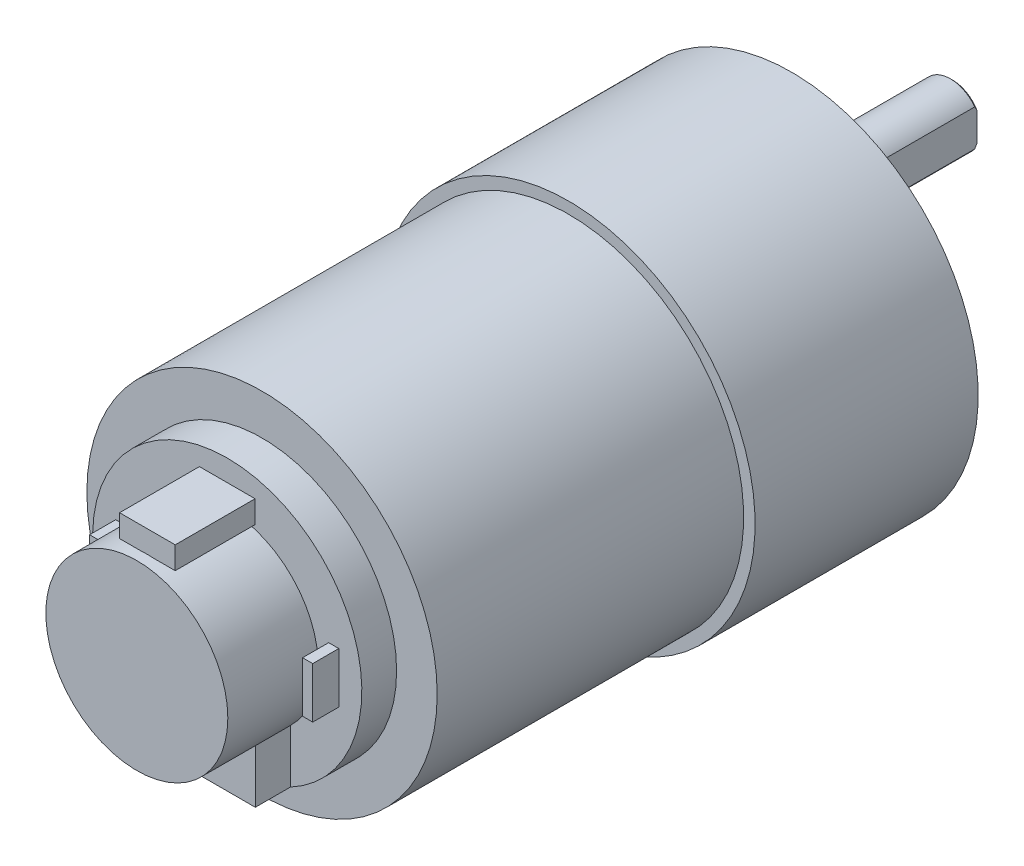
SolidWorks part; units mm, degrees
material "Plain Carbon Steel"
ref_plane "Front Plane" through (0, 0, 0) normal (0, 0, 1) x (1, 0, 0)
ref_plane "Top Plane" through (0, 0, 0) normal (0, 1, 0) x (1, 0, 0)
ref_plane "Right Plane" through (0, 0, 0) normal (1, 0, 0) x (0, 0, -1)
sketch "Sketch1" plane through (0, 0, 0) normal (0, 0, 1) x (1, 0, 0)
  line L0 (0, 0) -> (-7, 0)
  line L1 (0, 0) -> (-17.272, 0)
  line L2 (0, 0) -> (0, 17.272)
  line L3 (0, 0) -> (0, -15.5)
  line L4 (-4.6, 1.8) -> (-4.6, -1.8)
  line L5 (0, 0) -> (0, -15.5) construction
  circle A0 centre (0, 0) radius 17.272
  circle A1 centre (-7, 0) radius 3
  circle A2 centre (-7, 0) radius 6
  circle A3 centre (0, -15.5) radius 1.5
  circle A4 centre (-13.4234, -7.75) radius 1.5
  circle A5 centre (-13.4234, 7.75) radius 1.5
  circle A6 centre (0, 15.5) radius 1.5
  circle A7 centre (13.4234, 7.75) radius 1.5
  circle A8 centre (13.4234, -7.75) radius 1.5
  point P28 (0, -0.9391)
  point P31 (0, 0)
  point P35 (0, 0)
  dimension "D1" = 34.544
  dimension "D2" = 7
  dimension "D4" = 6
  dimension "D3" = 12
  dimension "D8" = 6
  dimension "D6" = 15.5
  dimension "D7" = 3
  dimension "D5" = 2.4
  dimension "D9" = 15.5
extrude "Boss-Extrude1" add sketch "Sketch1" along normal blind 52.22 contours A0
extrude "Boss-Extrude2" add sketch "Sketch1<3>" against normal blind 6.5 contours A2 A1 | L4 A1 L1 | L1 A1 L4 | L1 A2 A1 | L1 A1 L4 | L4 A1 L1 region at (-7, -5.8658, 0) region at (-2.5, 0.1342, 0) region at (-4.3578, -0.685, 0) region at (-4.3578, 0.685, 0) region at (-7.1451, -1.3055, 0) region at (-7.1451, 1.3055, 0)
sketch "Sketch1<3>" plane through (0, 0, 0) normal (0, 0, 1) x (1, 0, 0) same geometry as "Sketch1"
extrude "Boss-Extrude3" add sketch "Sketch1<4>" against normal blind 22.86 contours L4 A1 L1 | L1 A1 L4 region at (-7.1451, -1.3055, 0) region at (-7.1451, 1.3055, 0)
sketch "Sketch1<4>" plane through (0, 0, 0) normal (0, 0, 1) x (1, 0, 0) same geometry as "Sketch1"
extrude "Boss-Extrude4" add sketch "Sketch1<5>" against normal blind 10.668 contours L4 A1 | L4 A1 L1 region at (-4.3578, -0.685, 0) region at (-4.3578, 0.685, 0)
sketch "Sketch1<5>" plane through (0, 0, 0) normal (0, 0, 1) x (1, 0, 0) same geometry as "Sketch1"
sketch "Sketch2" plane through (0, 0, 52.22) normal (0, 0, 1) x (1, 0, 0)
  line L0 (0, 17.272) -> (0, -17.272) construction
  line L1 (17.272, 0) -> (-17.272, 0) construction
  line L2 (-11, 2.5) -> (-10, 2.5)
  line L3 (-11, 2.5) -> (-11, -2.5)
  line L4 (-11, -2.5) -> (-10, -2.5)
  line L5 (-10, 2.5) -> (-10, -2.5)
  line L6 (10, 2.5) -> (10, -2.5)
  line L7 (11, -2.5) -> (10, -2.5)
  line L8 (11, 2.5) -> (11, -2.5)
  line L9 (11, 2.5) -> (10, 2.5)
  circle A0 centre (0, 0) radius 17.272 construction
  dimension "D1" = 5
  dimension "D2" = 1
  dimension "D3" = 2.5
  dimension "D4" = 10
extrude "Boss-Extrude5" add sketch "Sketch2" along normal blind 6
sketch "Sketch4" plane through (0, 0, 0) normal (0, 0, -1) x (-1, 0, 0)
  circle A0 centre (0, 0) radius 18.4
  dimension "D1" = 36.8
extrude "Boss-Extrude6" add sketch "Sketch4" against normal blind 22
hole_wizard "Tap Drill for M3 Tap1" positions "Sketch8" profile "Sketch7" hole size "M3" standard "ISO"
sketch "Sketch8" plane through (0, 0, 0) normal (0, 0, -1) x (-1, 0, 0)
  point P0 (-13.4234, -7.75)
  point P3 (0, -15.5)
  point P6 (0, 15.5)
  point P9 (13.4234, 7.75)
  point P12 (13.4234, -7.75)
  point P15 (-13.4234, 7.75)
sketch "Sketch7" plane through (13.4234, -7.75, 0) normal (1, 0, 0) x (0, 1, 0)
  line L0 (0, 0) -> (0, 3.7511)
  line L1 (0, 3.7511) -> (1.25, 3)
  line L2 (1.25, 3) -> (1.25, 0)
  line L5 (1.25, 0) -> (0, 0)
  line L10 (0, 3.7511) -> (-1.25, 3) construction
  line L11 (0, -6.35) -> (0, 107.95) construction
  dimension "Hole Dia." = 2.5
  dimension "Hole Depth" = 3
  dimension "Drill Angle" = 118
sketch "Sketch9" plane through (0, 0, 52.22) normal (0, 0, 1) x (1, 0, 0)
  circle A0 centre (0, 0) radius 13.2715
  dimension "D1" = 26.543
extrude "Boss-Extrude7" add sketch "Sketch9" along normal blind 3.429
sketch "Sketch10" plane through (0, 0, 55.649) normal (0, 0, 1) x (1, 0, 0)
  circle A0 centre (0, 0) radius 8.9726
  dimension "D1" = 17.9451
extrude "Boss-Extrude8" add sketch "Sketch10" along normal blind 8.9154
sketch "Sketch11" plane through (0, 0, 55.649) normal (0, 0, 1) x (1, 0, 0)
  line L1 (6.223, -11.7221) -> (-6.223, -11.7221)
  line L2 (6.223, -11.7221) -> (6.223, -5.6769)
  line L3 (6.223, -5.6769) -> (-6.223, -5.6769)
  line L4 (-6.223, -11.7221) -> (-6.223, -5.6769)
  circle A0 centre (0, 0) radius 13.2715 construction
  circle A1 centre (0, 0) radius 13.2715 construction
  dimension "D1" = 6.0452
  dimension "D2" = 12.446
extrude "Boss-Extrude9" add sketch "Sketch11" along normal blind 3.4544
sketch "Sketch12" plane through (0, 0, 55.649) normal (0, 0, 1) x (1, 0, 0)
  line L1 (2.7432, 8.9535) -> (-2.7432, 8.9535)
  line L2 (2.7432, 8.9535) -> (2.7432, 11.1633)
  line L3 (2.7432, 11.1633) -> (-2.7432, 11.1633)
  line L4 (-2.7432, 8.9535) -> (-2.7432, 11.1633)
  arc A1 (6.223, -11.7221) -> (-6.223, -11.7221) centre (0, 0) ccw construction
  point P4 (0, 13.2715)
  point P5 (0, 11.1633)
  dimension "D1" = 5.4864
  dimension "D2" = 2.2098
  dimension "D3" = 4.318
extrude "Boss-Extrude10" add sketch "Sketch12" along normal blind 7.874
chamfer "Chamfer1" distance 0.2 angle 45 1 edges at (-10, 0, -22.86)
chamfer "Chamfer2" distance 0.5 angle 45 1 edges at (-1, 0, -6.5)
ref_plane "Plane1" through (-18.4, 0, 0) normal (-1, 0, 0) x (0, 0, 1)
